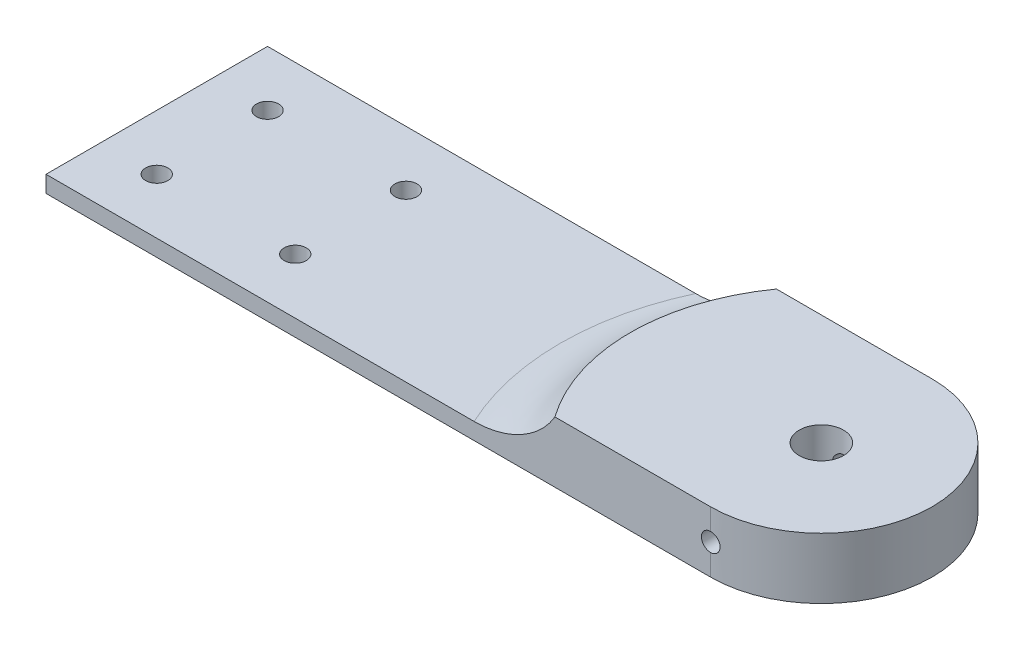
SolidWorks part; units mm, degrees
material "1060 Alloy"
ref_plane "Front Plane" through (0, 0, 0) normal (0, 0, 1) x (1, 0, 0)
ref_plane "Top Plane" through (0, 0, 0) normal (0, 1, 0) x (1, 0, 0)
ref_plane "Right Plane" through (0, 0, 0) normal (1, 0, 0) x (0, 0, -1)
sketch "Sketch1" plane through (0, 0, 0) normal (0, 1, 0) x (1, 0, 0)
  line L0 (-120, 20) -> (20, 20)
  line L1 (20, 20) -> (20, -5)
  line L2 (20, -5) -> (-120, -5) construction
  line L3 (-120, -5) -> (-120, 20)
  line L4 (20, -5) -> (20, -20)
  line L5 (20, -20) -> (-120, -20)
  line L6 (-120, -20) -> (-120, -5)
  line L7 (20, -10) -> (-110, -10) construction
  line L8 (-110, -10) -> (-110, -5) construction
  line L9 (-110, -5) -> (-110, 10) construction
  line L10 (-110, 10) -> (20, 10) construction
  circle A0 centre (0, 0) radius 4
  circle A1 centre (-110, 10) radius 2
  circle A2 centre (-85, 10) radius 2
  circle A3 centre (-85, -10) radius 2
  circle A4 centre (-110, -10) radius 2
  arc A5 (0, -20) -> (0, 20) centre (0, 0) ccw
  dimension "D1" = 8
  dimension "D7" = 4
  dimension "D2" = 20
  dimension "D3" = 25
  dimension "D4" = 20
  dimension "D5" = 15
  dimension "D6" = 140
  dimension "D9" = 25
  dimension "D8" = 10
extrude "Boss-Extrude1" add sketch "Sketch1" along normal blind 11 contours L5 A5 L0 L3 L6 A4 A3 A2 A1 A0 region at (-52.1353, 0, 0)
sketch "Sketch4" plane through (0, 11, 0) normal (0, 1, 0) x (1, 0, 0)
  line L0 (-28.1114, 20) -> (-120, 20)
  line L1 (-120, 20) -> (-120, -20)
  line L2 (-120, -20) -> (-28.1114, -20)
  arc A1 (-28.1114, 20) -> (-28.1114, -20) centre (0, 0) ccw
  dimension "D1" = 69
extrude "Cut-Extrude1" cut sketch "Sketch4" against normal offset from surface (8 mm away) 3 up to face at (-110, 0, 12)
fillet "Fillet2" radius 14 1 edges at (-34.5, 3, 0)
hole_wizard "M4 Tapped Hole1" positions "Sketch2" profile "Sketch3" tap size "M4" standard "ISO" end condition through all
sketch "Sketch2" plane through (0, 0, -20) normal (0, 0, -1) x (-1, 0, 0)
  line L0 (0, 6.6137) -> (0, -6.6137) construction
  line L1 (0, 11) -> (0, 0) construction
  point P0 (0, 5.5)
  point P11 (0, 5.5)
cosmetic thread "Hole Thread1" parameters "D2"=4
sketch "Sketch3" plane through (0, 5.5, -20) normal (1, 0, 0) x (0, 1, 0)
  line L0 (0, 0) -> (0, 40)
  line L1 (0, 40) -> (1.65, 40)
  line L2 (1.65, 40) -> (1.65, 0)
  line L5 (1.65, 0) -> (0, 0)
  line L11 (0, -6.35) -> (0, 107.95) construction
  dimension "Thru Tap Drill Dia." = 3.3
  dimension "Thru Tap Drill Depth" = 40
